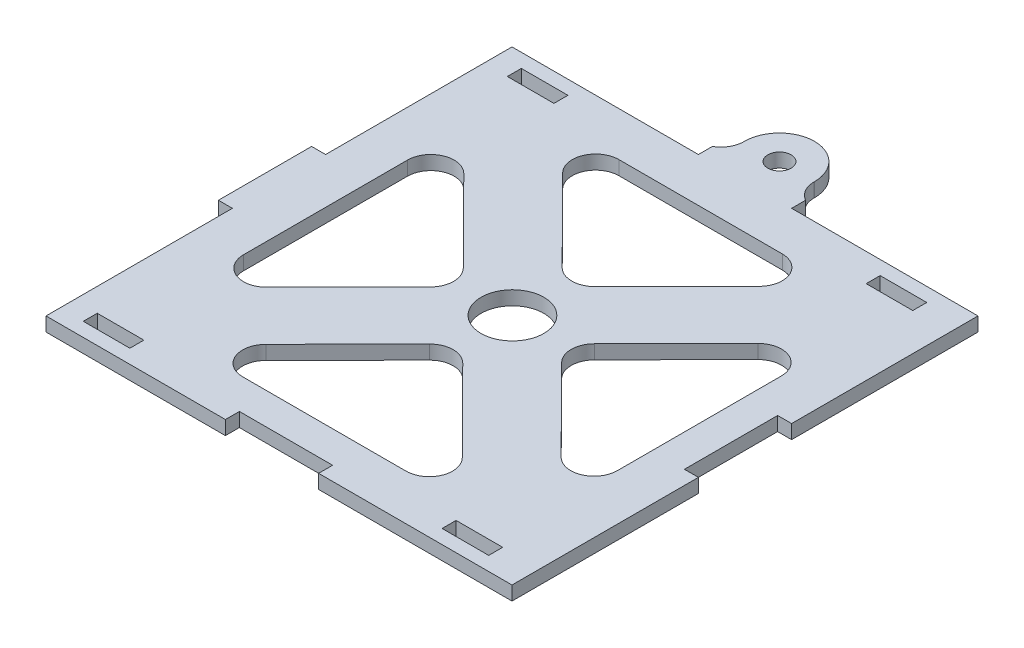
SolidWorks part; units mm, degrees
other "Markup1"
sketch "Sketch2" plane through (-50, 3, 50.5) normal (-0.0452, 0.9955, 0.0839) x (0.997, 0.0397, 0.066)
other "Markup2"
sketch "Sketch4" plane through (-50.5908, 3, 51.1584) normal (-0.0214, 0.9991, 0.0362) x (0.9834, 0.0145, 0.1809)
material "polywood"
ref_plane "Front Plane" through (0, 0, 0) normal (0, 0, 1) x (1, 0, 0)
ref_plane "Top Plane" through (0, 0, 0) normal (0, 1, 0) x (1, 0, 0)
ref_plane "Right Plane" through (0, 0, 0) normal (1, 0, 0) x (0, 0, -1)
sketch "Sketch1" plane through (0, 0, 0) normal (0, 1, 0) x (1, 0, 0)
  line L0 (-29.5455, -40.3709) -> (-4.0436, -14.7089)
  line L1 (-49.9389, -50.1584) -> (50.0611, -50.1584)
  line L2 (-49.9389, -50.1584) -> (-49.9389, -10.1584)
  line L3 (-49.9389, 49.8416) -> (-9.9389, 49.8416)
  line L4 (50.0611, -50.1584) -> (50.0611, -10.1584)
  line L5 (-40.119, -40.3709) -> (40.119, 40.3709) construction
  line L6 (-40.119, 40.3709) -> (5.2868, -5.32) construction
  line L7 (-40.119, -40.3709) -> (40.119, -40.3709)
  line L8 (-40.119, -40.3709) -> (-40.119, 40.3709)
  line L9 (-40.119, 40.3709) -> (40.119, 40.3709)
  line L10 (40.119, -40.3709) -> (40.119, 40.3709)
  line L11 (-40.119, -40.3709) -> (40.119, 40.3709) construction
  line L12 (-40.119, 40.3709) -> (40.119, -40.3709) construction
  line L13 (-33.0737, -22.6413) -> (-14.6833, -4.1355)
  line L14 (40.119, -29.7309) -> (14.6833, -4.1355)
  line L15 (22.8848, -33.6684) -> (4.0436, -14.7089)
  line L16 (-33.0737, -22.6413) -> (-40.119, -29.7309)
  line L17 (22.8848, -33.6684) -> (29.5455, -40.3709)
  line L18 (-5.2868, -5.32) -> (-5.3199, -5.2867)
  line L19 (5.2868, -5.32) -> (6.3448, -4.2553)
  line L20 (-4.295, 6.318) -> (-5.2868, 5.32)
  line L21 (-14.6833, 4.1355) -> (-40.119, 29.7309)
  line L22 (5.3199, 5.2867) -> (5.2868, 5.32)
  line L23 (14.6833, 4.1355) -> (40.119, 29.7309)
  line L24 (7.8444, -7.8937) -> (40.119, -40.3709) construction
  line L25 (4.0436, 14.7089) -> (29.5455, 40.3709)
  line L26 (-4.0436, 14.7089) -> (-29.5455, 40.3709)
  line L27 (-14.6833, 4.1355) -> (-10.5736, 0)
  line L44 (10.0611, 49.8416) -> (50.0611, 49.8416)
  line L45 (-9.9389, 52.8416) -> (-7.4389, 52.8416)
  line L46 (-9.9389, 52.8416) -> (-9.9389, 49.8416)
  line L48 (10.0611, 52.8416) -> (10.0611, 49.8416)
  line L49 (-9.9389, 52.8416) -> (10.0611, 49.8416) construction
  line L50 (-9.9389, 49.8416) -> (10.0611, 52.8416) construction
  line L51 (-7.4389, 52.8416) -> (-7.4389, 57.2431)
  line L52 (7.5611, 57.2431) -> (7.5611, 52.8416)
  line L53 (7.5611, 52.8416) -> (10.0611, 52.8416)
  line L54 (50.0611, 9.8416) -> (50.0611, 49.8416)
  line L55 (47.0611, 9.8416) -> (50.0611, 9.8416)
  line L56 (47.0611, 9.8416) -> (47.0611, -10.1584)
  line L57 (47.0611, -10.1584) -> (50.0611, -10.1584)
  line L59 (-52.9389, 9.8416) -> (-49.9389, 9.8416)
  line L60 (-52.9389, 9.8416) -> (-52.9389, -10.1584)
  line L61 (-52.9389, -10.1584) -> (-49.9389, -10.1584)
  line L63 (-49.9389, 9.8416) -> (-49.9389, 49.8416)
  line L64 (-10.5736, 0) -> (-14.6833, -4.1355)
  line L65 (-44.9389, 46.8416) -> (-34.9389, 46.8416)
  line L66 (-44.9389, 46.8416) -> (-44.9389, 43.8416)
  line L67 (-44.9389, 43.8416) -> (-34.9389, 43.8416)
  line L68 (-34.9389, 46.8416) -> (-34.9389, 43.8416)
  line L69 (-44.9389, 46.8416) -> (-34.9389, 43.8416) construction
  line L70 (-44.9389, 43.8416) -> (-34.9389, 46.8416) construction
  line L71 (32.0611, 46.8416) -> (42.0611, 46.8416)
  line L72 (32.0611, 46.8416) -> (32.0611, 43.8416)
  line L73 (32.0611, 43.8416) -> (42.0611, 43.8416)
  line L74 (42.0611, 46.8416) -> (42.0611, 43.8416)
  line L75 (32.0611, 46.8416) -> (42.0611, 43.8416) construction
  line L76 (32.0611, 43.8416) -> (42.0611, 46.8416) construction
  line L77 (32.0611, -47.1584) -> (32.0611, -44.1584)
  line L78 (32.0611, -47.1584) -> (42.0611, -47.1584)
  line L79 (42.0611, -47.1584) -> (42.0611, -44.1584)
  line L80 (32.0611, -44.1584) -> (42.0611, -44.1584)
  line L81 (-44.9389, -47.1584) -> (-44.9389, -44.1584)
  line L82 (-44.9389, -47.1584) -> (-34.9389, -47.1584)
  line L83 (-34.9389, -47.1584) -> (-34.9389, -44.1584)
  line L84 (-44.9389, -44.1584) -> (-34.9389, -44.1584)
  line L85 (-4.0436, -14.7089) -> (0, -10.6399)
  line L86 (0, -10.6399) -> (4.0436, -14.7089)
  line L87 (14.6833, -4.1355) -> (10.5736, 0)
  line L88 (10.5736, 0) -> (14.6833, 4.1355)
  line L89 (4.0436, 14.7089) -> (0, 10.6399)
  line L90 (0, 10.6399) -> (-4.0436, 14.7089)
  circle A0 centre (0, 0) radius 6.7367
  arc A5 (-7.4389, 57.2431) -> (7.5611, 57.2431) centre (0.0611, 57.2431) cw
  circle A6 centre (0.0611, 57.2431) radius 2.5
  point P0 (0, 0)
  point P6 (0, 0)
  point P18 (-3.3571, -10.6101)
  point P20 (2.5558, 10.8311)
  point P23 (10.6712, -3.1577)
  point P26 (-10.7136, 3.0105)
  point P54 (-39.9389, 45.3416)
  point P57 (45.416, 6.4678)
  point P60 (37.0611, 45.3416)
  point P63 (0.0611, 51.3416)
  point P75 (11.1152, -0.545)
  point P79 (11.1152, 0.545)
  point P82 (0.4755, 11.1184)
  point P85 (-0.4755, 11.1184)
  point P88 (-11.1152, 0.545)
  point P100 (32.0611, -45.6584)
  dimension "D4" = 15
  dimension "D5" = 15
extrude "Boss-Extrude1" add sketch "Sketch1" along normal blind 3 contours L14 L23 L10 L9 L25 L26 L8 L21 L13 L16 L7 L0 L15 L17 A0 | L1 L4 L3 L2 L10 L7 L8 L9 region at (-34.8322, 0, 39.2326) region at (-48.3958, 0, 30.1584)
fillet "Fillet1" radius 5 14 edges at (-29.5455, 1.5, -40.3709) (29.5455, 1.5, -40.3709) (40.119, 1.5, -29.7309) (40.119, 1.5, 29.7309) (29.5455, 1.5, 40.3709) (-29.5455, 1.5, 40.3709) (-40.119, 1.5, -29.7309) (-40.119, 1.5, 29.7309) (-10.5736, 1.5, 0) (0, 1.5, 10.6399) (10.5736, 1.5, 0) (0, 1.5, -10.6399) (7.5611, 1.5, -52.8416) (-7.4389, 1.5, -52.8416)
sketch "Sketch5" plane through (0, 0, 50.1584) normal (0, 0, 1) x (1, 0, 0)
  line L1 (8.5611, 3) -> (-11.4389, 3)
  line L35 (-52.9389, 61.5) -> (-52.9389, 41.5)
  line L75 (-52.9389, 41.5) -> (-49.9389, 41.5)
  line L80 (-49.9389, 41.5) -> (-49.9389, 3)
  line L103 (-49.9389, 3) -> (-11.4389, 3)
  line L104 (-11.4389, 3) -> (-11.4389, 0)
  line L105 (-11.4389, 0) -> (8.5611, 0)
  line L106 (8.5611, 0) -> (8.5611, 3)
  line L107 (-49.9389, 100) -> (-49.9389, 61.5)
  line L108 (47.0611, 61.5) -> (47.0611, 100)
  line L109 (47.0611, 41.5) -> (50.0611, 41.5)
  line L110 (50.0611, 41.5) -> (50.0611, 61.5)
  line L111 (50.0611, 61.5) -> (47.0611, 61.5)
  line L112 (-49.9389, 100) -> (-49.9389, 61.5)
  line L113 (-11.4389, 100) -> (-49.9389, 100)
  line L114 (8.5611, 100) -> (8.5611, 103)
  line L115 (8.5611, 103) -> (-11.4389, 103)
  line L116 (-11.4389, 103) -> (-11.4389, 100)
  line L117 (8.5611, 3) -> (47.0611, 3)
  line L118 (8.5611, 3) -> (47.0611, 3)
  line L119 (-49.9389, 61.5) -> (-52.9389, 61.5)
  line L120 (-52.9389, 61.5) -> (-52.9389, 41.5)
  line L121 (-52.9389, 41.5) -> (-49.9389, 41.5)
  line L122 (-49.9389, 41.5) -> (-49.9389, 3)
  line L124 (-11.4389, 3) -> (-11.4389, 0)
  line L125 (-11.4389, 0) -> (8.5611, 0)
  line L126 (8.5611, 0) -> (8.5611, 3)
  line L128 (47.0611, 61.5) -> (47.0611, 100)
  line L129 (47.0611, 41.5) -> (50.0611, 41.5)
  line L130 (50.0611, 41.5) -> (50.0611, 61.5)
  line L131 (50.0611, 61.5) -> (47.0611, 61.5)
  line L133 (-11.4389, 100) -> (-49.9389, 100)
  line L134 (8.5611, 100) -> (8.5611, 103)
  line L135 (8.5611, 103) -> (-11.4389, 103)
  line L136 (-11.4389, 103) -> (-11.4389, 100)
  line L139 (-49.9389, 61.5) -> (-52.9389, 61.5)
  line L161 (47.0611, 3) -> (47.0611, 41.5)
  line L162 (47.0611, 3) -> (47.0611, 41.5)
  line L163 (47.0611, 100) -> (8.5611, 100)
  line L164 (47.0611, 100) -> (8.5611, 100)
  dimension "D1" = 0
extrude "Cut-Extrude1" cut sketch "Sketch5" against normal blind 3 contours L1 L124 L125 L126
